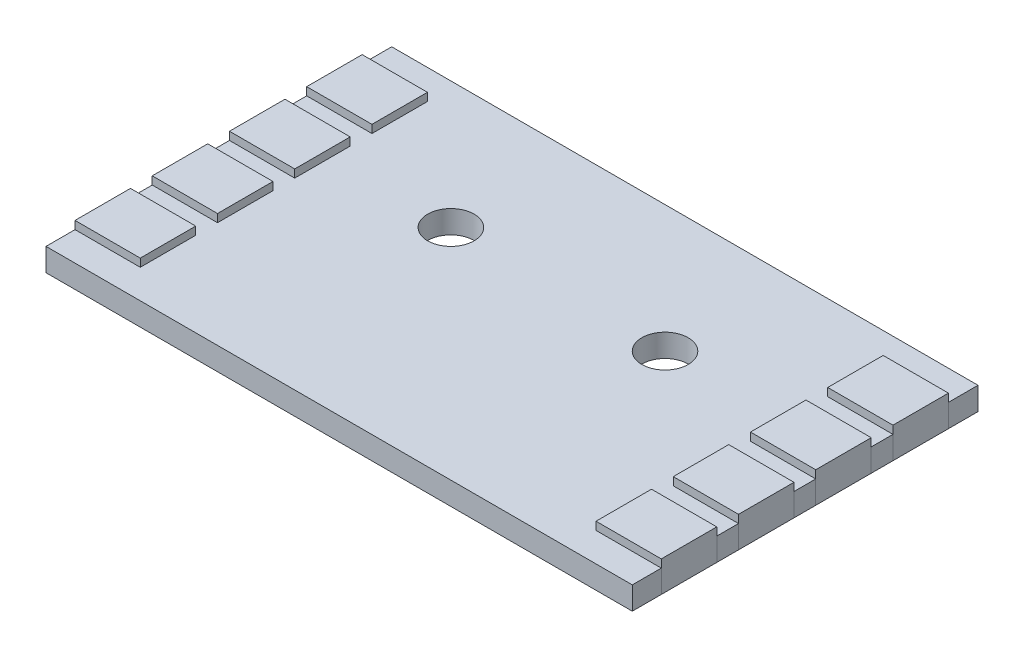
SolidWorks part; units mm, degrees
ref_plane "Front Plane" through (0, 0, 0) normal (0, 0, 1) x (1, 0, 0)
ref_plane "Top Plane" through (0, 0, 0) normal (0, 1, 0) x (1, 0, 0)
ref_plane "Right Plane" through (0, 0, 0) normal (1, 0, 0) x (0, 0, -1)
sketch "Sketch1" plane through (0, 0, 0) normal (0, 1, 0) x (1, 0, 0)
  line L0 (41.0718, -16.7767) -> (41.0718, -12.8905)
  line L1 (0, 0) -> (41.0718, 0)
  line L2 (0, 0) -> (0, -24.2189)
  line L3 (0, -24.2189) -> (41.0718, -24.2189)
  line L4 (41.0718, 0) -> (41.0718, -24.2189)
  line L5 (41.0718, -22.1869) -> (36.4998, -22.1869)
  line L6 (41.0718, -22.1869) -> (41.0718, -18.3007)
  line L7 (41.0718, -18.3007) -> (36.4998, -18.3007)
  line L8 (36.4998, -22.1869) -> (36.4998, -18.3007)
  line L9 (41.0718, -16.7767) -> (36.4998, -16.7767)
  line L10 (36.4998, -16.7767) -> (36.4998, -12.8905)
  line L11 (41.0718, -12.8905) -> (36.4998, -12.8905)
  line L12 (41.0718, -11.3665) -> (41.0718, -7.4803)
  line L13 (41.0718, -11.3665) -> (36.4998, -11.3665)
  line L14 (36.4998, -11.3665) -> (36.4998, -7.4803)
  line L15 (41.0718, -7.4803) -> (36.4998, -7.4803)
  line L16 (41.0718, -5.9563) -> (41.0718, -2.0701)
  line L17 (41.0718, -5.9563) -> (36.4998, -5.9563)
  line L18 (36.4998, -5.9563) -> (36.4998, -2.0701)
  line L19 (41.0718, -2.0701) -> (36.4998, -2.0701)
  line L20 (20.5359, 0) -> (20.5359, -24.2189) construction
  line L21 (0, -18.3007) -> (4.572, -18.3007)
  line L22 (4.572, -22.1869) -> (4.572, -18.3007)
  line L23 (0, -22.1869) -> (4.572, -22.1869)
  line L24 (0, -22.1869) -> (0, -18.3007)
  line L25 (0, -16.7767) -> (4.572, -16.7767)
  line L26 (4.572, -16.7767) -> (4.572, -12.8905)
  line L27 (0, -12.8905) -> (4.572, -12.8905)
  line L28 (0, -16.7767) -> (0, -12.8905)
  line L29 (0, -11.3665) -> (4.572, -11.3665)
  line L30 (4.572, -11.3665) -> (4.572, -7.4803)
  line L31 (0, -7.4803) -> (4.572, -7.4803)
  line L32 (0, -11.3665) -> (0, -7.4803)
  line L33 (0, -5.9563) -> (4.572, -5.9563)
  line L34 (4.572, -5.9563) -> (4.572, -2.0701)
  line L35 (0, -2.0701) -> (4.572, -2.0701)
  line L36 (0, -5.9563) -> (0, -2.0701)
  circle A0 centre (13.0359, -8.89) radius 1.6256
  circle A1 centre (28.0359, -8.89) radius 1.6256
  dimension "D4" = 3.2512
  dimension "D1" = 41.0718
  dimension "D2" = 24.2189
  dimension "D3" = 15
  dimension "D6" = 13.0359
  dimension "D5" = 8.89
  dimension "D7" = 3.8862
  dimension "D8" = 4.572
  dimension "D9" = 2.032
  dimension "D11" = 1.524
  dimension "D10" = 4
extrude "Boss-Extrude1" add sketch "Sketch1" along normal blind 1.6 contours L20 L1 L2 L35 L34 L33 L31 L30 L29 L27 L26 L25 L21 L22 L23 L3 A0 | L1 L20 L3 L4 L5 L8 L7 L9 L10 L11 L13 L14 L15 L17 L18 L19 A1 region at (29.5016, 0, 12.1702) region at (11.5702, 0, 12.1702)
extrude "Boss-Extrude2" add sketch "Sketch1<3>" along normal blind 2.159 separate body contours L35 L2 L33 L34 | L31 L2 L29 L30 | L27 L2 L25 L26 | L2 L23 L22 L21 | L8 L5 L4 L7 | L0 L11 L10 L9 | L4 L15 L14 L13 | L4 L19 L18 L17 region at (38.7858, 0, 14.8336) region at (38.7858, 0, 20.2438) region at (38.7858, 0, 9.4234) region at (38.7858, 0, 4.0132) region at (2.286, 0, 20.2438) region at (2.286, 0, 14.8336) region at (2.286, 0, 4.0132) region at (2.286, 0, 9.4234)
sketch "Sketch1<3>" plane through (0, 0, 0) normal (0, 1, 0) x (1, 0, 0) same geometry as "Sketch1"
equation "\"D6@Sketch1\"=(\"D1@Sketch1\"-\"D3@Sketch1\")/2"
